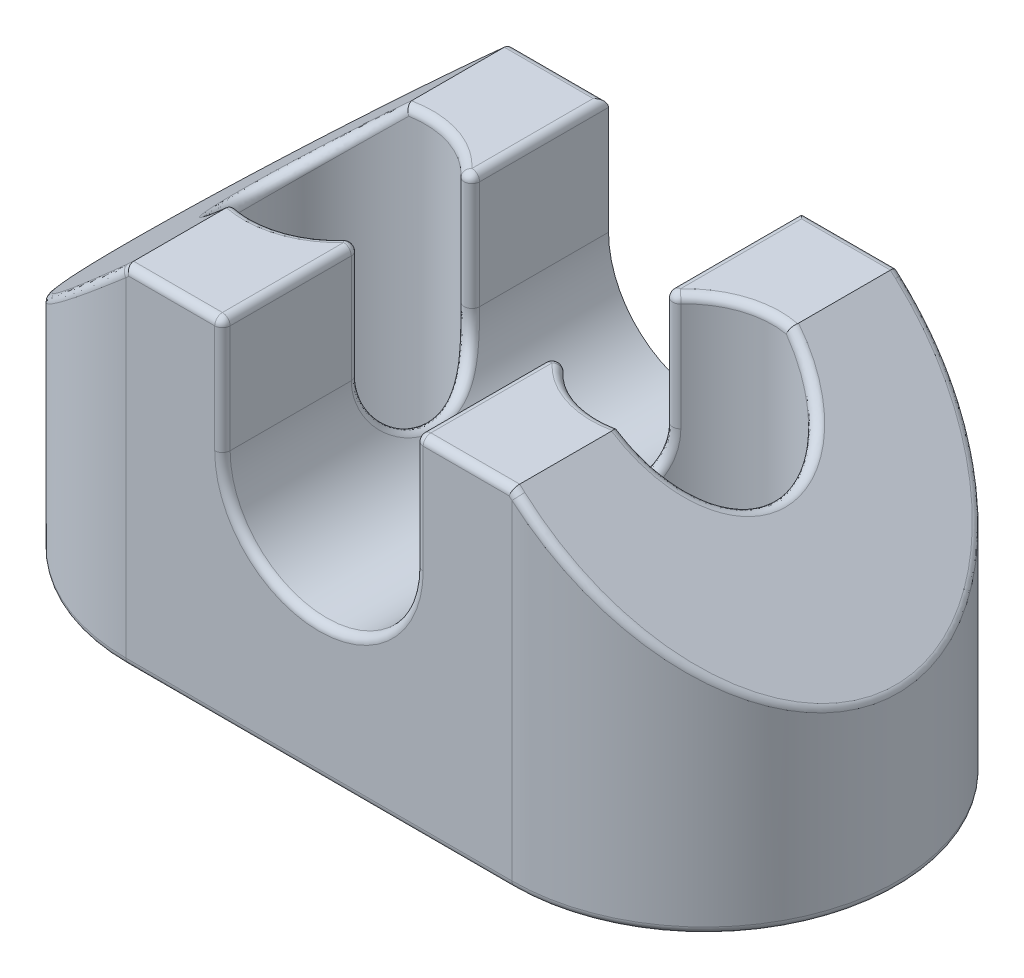
SolidWorks part; units mm, degrees
ref_plane "Plano frontal" through (0, 0, 0) normal (0, 0, 1) x (1, 0, 0)
ref_plane "Plano superior" through (0, 0, 0) normal (0, 1, 0) x (1, 0, 0)
ref_plane "Plano direito" through (0, 0, 0) normal (1, 0, 0) x (0, 0, -1)
sketch "Sketch1" plane through (0, 0, 0) normal (0, 1, 0) x (1, 0, 0)
  line L1 (0, 0) -> (10, 0)
  line L3 (0, 10) -> (10, 10)
  arc A2 (0, 10) -> (0, 0) centre (0, 5) ccw
  arc A3 (10, 0) -> (10, 10) centre (10, 5) ccw
  point P3 (0, 0)
  point P4 (0, 0)
  dimension "D1" = 10
  dimension "D2" = 5
extrude "Boss-Extrude3" add sketch "Sketch1" along normal blind 9
sketch "Sketch3" plane through (0, 0, 0) normal (0, 0, 1) x (1, 0, 0)
  line L0 (0, 9) -> (-5, 4.5)
  line L2 (-5, 9) -> (-5, 0) construction
  line L3 (5, 9) -> (5, 0) construction
  line L4 (0, 9) -> (10, 9) construction
  line L5 (0, 0) -> (10, 0) construction
  line L6 (10, 9) -> (15, 4.5)
  line L7 (15, 0) -> (15, 9) construction
  line L8 (15, 9) -> (10, 9) construction
  line L9 (0, 9) -> (-5, 9) construction
  line L10 (15, 4.5) -> (15, 9)
  line L11 (-5, 9) -> (-5, 4.5)
  line L12 (15, 9) -> (10, 9)
  line L13 (0, 9) -> (-5, 9)
extrude "Cut-Extrude1" cut sketch "Sketch3" against normal up to surface (10 mm away) up to face at (5, 4.5, -10)
sketch "Sketch4" plane through (0, 9, 0) normal (0, 1, 0) x (1, 0, 0)
  line L0 (0, 10) -> (0, 0) construction
  line L1 (0, 0) -> (10, 0) construction
  circle A0 centre (0.5, 5) radius 2.25
  circle A1 centre (9.5, 5) radius 2.25
  point P8 (0, 0)
  dimension "D1" = 4.5
  dimension "D2" = 4.5
  dimension "D5" = 5
  dimension "D3" = 9
  dimension "D4" = 0.5
extrude "Cut-Extrude2" cut sketch "Sketch4" against normal through all
sketch "Sketch5" plane through (0, 0, 0) normal (0, 0, 1) x (1, 0, 0)
  line L0 (2.5, 9) -> (7.5, 9)
  line L1 (0, 9) -> (10, 9) construction
  line L2 (2.5, 9) -> (2.5, 6)
  line L3 (7.5, 6) -> (7.5, 9)
  line L4 (0, 9) -> (0, 0) construction
  arc A0 (2.5, 6) -> (7.5, 6) centre (5, 6) ccw
  dimension "D2" = 2.5
  dimension "D1" = 5
  dimension "D3" = 2.5
  dimension "D4" = 3
extrude "Cut-Extrude3" cut sketch "Sketch5" against normal through all
fillet "Fillet1" radius 0.2 25 edges at (7.5, 7.5, 0) (5, 3.5, 0) (1.25, 9, -10) (8.75, 9, -10) (15, 4.5, -5) (8.75, 9, 0) (2.5, 7.5, 0) (1.25, 9, 0) (-5, 4.5, -5) (7.5, 7.5, -3.9692) (7.252, 4.9144, -4.905) (2.5, 7.5, -3.9692) (2.748, 4.9144, -5.095) (7.5, 7.5, -6.0308) (2.5, 7.5, -6.0308) (11.75, 7.425, -5) (-1.75, 7.425, -5) (1.449, 9, -7.0401) (8.551, 9, -7.0401) (8.551, 9, -2.9599) (1.449, 9, -2.9599) (2.5, 9, -1.9846) (7.5, 9, -1.9846) (7.5, 9, -8.0154) (2.5, 9, -8.0154)
fillet "Fillet2" radius 0.2 4 edges at (-5, 0, -5) (5, 0, -10) (15, 0, -5) (5, 0, 0)
